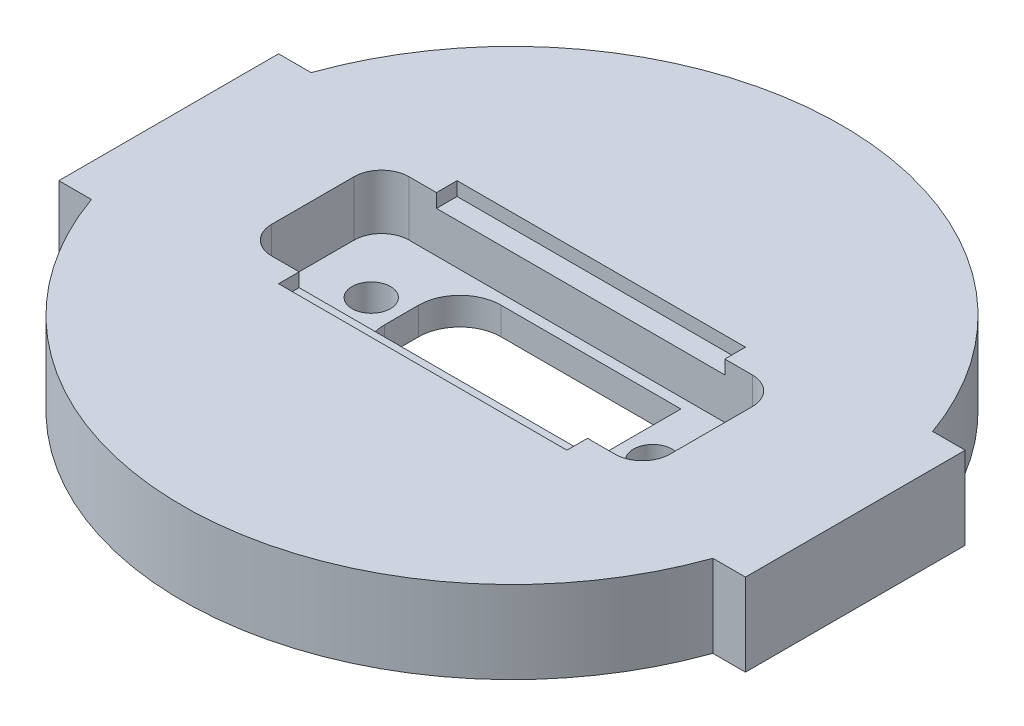
SolidWorks part; units mm, degrees
ref_plane "Płaszczyzna przednia" through (0, 0, 0) normal (0, 0, 1) x (1, 0, 0)
ref_plane "Płaszczyzna górna" through (0, 0, 0) normal (0, 1, 0) x (1, 0, 0)
ref_plane "Płaszczyzna prawa" through (0, 0, 0) normal (1, 0, 0) x (0, 0, -1)
sketch "Sketch1" plane through (0, 0, 0) normal (0, 1, 0) x (1, 0, 0)
  line L5 (22.6274, 8) -> (25, 8)
  line L6 (-25, -8) -> (-22.6274, -8)
  line L12 (-25, -8) -> (-25, 8)
  line L13 (-25, 8) -> (-22.6274, 8)
  line L14 (25, -8) -> (25, 8)
  line L15 (-25, -8) -> (25, 8) construction
  line L16 (-25, 8) -> (25, -8) construction
  line L17 (22.6274, -8) -> (25, -8)
  arc A0 (-22.6274, -8) -> (22.6274, -8) centre (0, 0) ccw
  arc A1 (22.6274, 8) -> (-22.6274, 8) centre (0, 0) ccw
  dimension "D1" = 50
  dimension "D2" = 16
extrude "Boss-Extrude1" add sketch "Sketch1" along normal blind 6
sketch "Sketch2" plane through (0, 6, 0) normal (0, 1, 0) x (1, 0, 0)
  line L9 (-5.05, -4.25) -> (8.05, -4.25)
  line L10 (-8.05, -1.25) -> (-8.05, 1.25)
  line L11 (-5.05, 4.25) -> (8.05, 4.25)
  line L12 (8.05, -4.25) -> (8.05, 4.25)
  line L13 (-8.05, -4.25) -> (8.05, 4.25) construction
  line L14 (-8.05, 4.25) -> (8.05, -4.25) construction
  arc A2 (-5.05, -4.25) -> (-8.05, -1.25) centre (-5.05, -1.25) cw
  arc A3 (-8.05, 1.25) -> (-5.05, 4.25) centre (-5.05, 1.25) cw
  point P0 (0, 0)
  dimension "D1" = 16.1
  dimension "D3" = 3
  dimension "D2" = 8.5
extrude "Cut-Extrude1" cut sketch "Sketch2" against normal blind 10
sketch "Sketch3" plane through (0, 6, 0) normal (0, 1, 0) x (1, 0, 0)
  line L1 (-12.5, -5) -> (12.5, -5)
  line L2 (-14.5, -3) -> (-14.5, 3)
  line L3 (-12.5, 5) -> (12.5, 5)
  line L4 (14.5, -3) -> (14.5, 3)
  line L5 (-14.5, -5) -> (14.5, 5) construction
  line L6 (-14.5, 5) -> (14.5, -5) construction
  arc A0 (12.5, 5) -> (14.5, 3) centre (12.5, 3) cw
  arc A1 (12.5, -5) -> (14.5, -3) centre (12.5, -3) ccw
  arc A2 (-12.5, -5) -> (-14.5, -3) centre (-12.5, -3) cw
  arc A3 (-14.5, 3) -> (-12.5, 5) centre (-12.5, 3) cw
  point P0 (0, 0)
  dimension "D3" = 2
  dimension "D1" = 29
  dimension "D2" = 10
extrude "Cut-Extrude2" cut sketch "Sketch3" against normal blind 4
sketch "Sketch4" plane through (0, 6, 0) normal (0, 1, 0) x (1, 0, 0)
  line L1 (-10.5, -6.5) -> (10.5, -6.5)
  line L2 (-10.5, -6.5) -> (-10.5, 6.5)
  line L3 (-10.5, 6.5) -> (10.5, 6.5)
  line L4 (10.5, -6.5) -> (10.5, 6.5)
  line L5 (-10.5, -6.5) -> (10.5, 6.5) construction
  line L6 (-10.5, 6.5) -> (10.5, -6.5) construction
  point P0 (0, 0)
  dimension "D1" = 13
  dimension "D2" = 21
extrude "Cut-Extrude3" cut sketch "Sketch4" against normal blind 1
sketch "Sketch5" plane through (0, 2, 0) normal (0, 1, 0) x (1, 0, 0)
  line L0 (0, 0) -> (-10.25, 0) construction
  line L1 (0, 0) -> (10.25, 0) construction
  circle A0 centre (-10.25, 0) radius 1.4
  circle A1 centre (10.25, 0) radius 1.4
extrude "Cut-Extrude4" cut sketch "Sketch5" against normal blind 10
